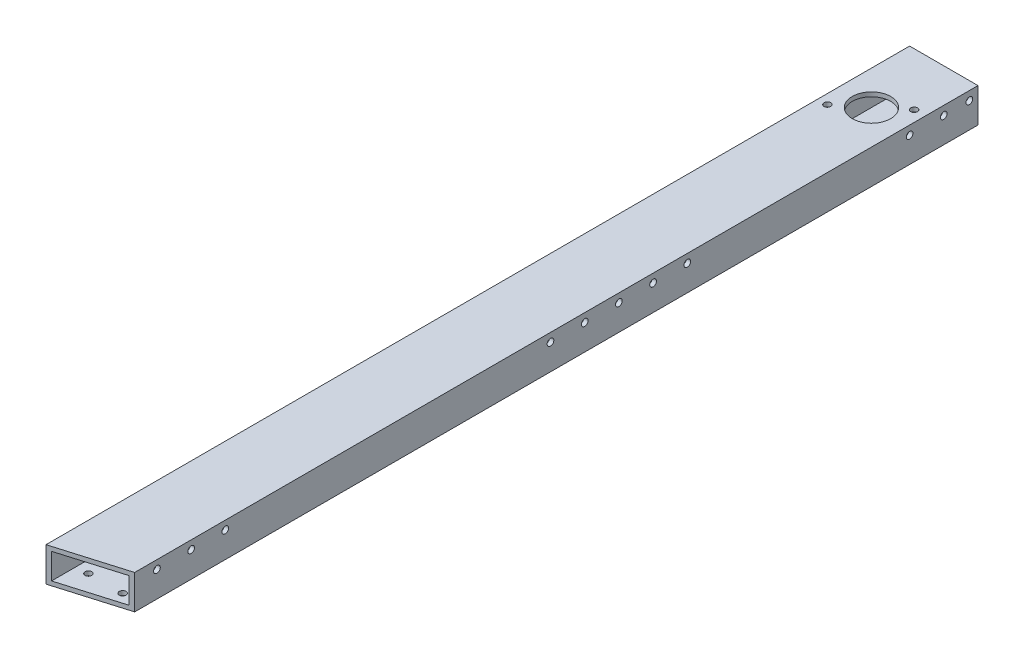
SolidWorks part; units mm, degrees
ref_plane "Front Plane" through (0, 0, 0) normal (0, 0, 1) x (1, 0, 0)
ref_plane "Top Plane" through (0, 0, 0) normal (0, 1, 0) x (1, 0, 0)
ref_plane "Right Plane" through (0, 0, 0) normal (1, 0, 0) x (0, 0, -1)
sketch "Sketch1" plane through (0, 0, 0) normal (0, 0, 1) x (1, 0, 0)
  line L0 (-22.225, 9.525) -> (22.225, 9.525)
  line L2 (-25.4, 12.7) -> (25.4, 12.7)
  line L3 (-25.4, 12.7) -> (-25.4, -12.7)
  line L4 (-25.4, -12.7) -> (25.4, -12.7)
  line L5 (25.4, 12.7) -> (25.4, -12.7)
  line L10 (22.225, 9.525) -> (22.225, -9.525)
  line L11 (-22.225, -9.525) -> (22.225, -9.525)
  line L12 (-22.225, 9.525) -> (-22.225, -9.525)
  point P12 (0, 12.7)
  point P14 (25.4, 0)
  dimension "Wall Thickness" = 3.175
  dimension "Outside Width" = 50.8
  dimension "Outside Height" = 25.4
  dimension "Inside Height" = 19.05
  dimension "Inside Width" = 44.45
sketch "Sketch2" plane through (0, 0, 0) normal (1, 0, 0) x (0, 0, -1)
  line L0 (320.675, 0) -> (-320.675, 0)
  point P4 (0, 0)
  point P7 (-320.675, 0)
  point P10 (320.675, 0)
  dimension "Length" = 641.35
sketch "Sketch3" plane through (0, 0, 0) normal (0, 0, 1) x (1, 0, 0)
  line L21 (25.4, 12.7) -> (-25.4, 12.7)
  line L22 (25.4, -12.7) -> (25.4, 12.7)
  line L23 (-25.4, -12.7) -> (25.4, -12.7)
  line L24 (-25.4, 12.7) -> (-25.4, -12.7)
  line L25 (25.4, 12.7) -> (-25.4, 12.7)
  line L26 (25.4, -12.7) -> (25.4, 12.7)
  line L27 (-25.4, -12.7) -> (25.4, -12.7)
  line L28 (-25.4, 12.7) -> (-25.4, -12.7)
  line L29 (22.225, 9.525) -> (-22.225, 9.525)
  line L30 (22.225, -9.525) -> (22.225, 9.525)
  line L31 (-22.225, -9.525) -> (22.225, -9.525)
  line L32 (-22.225, 9.525) -> (-22.225, -9.525)
  line L33 (22.225, 9.525) -> (-22.225, 9.525)
  line L34 (22.225, -9.525) -> (22.225, 9.525)
  line L35 (-22.225, -9.525) -> (22.225, -9.525)
  line L36 (-22.225, 9.525) -> (-22.225, -9.525)
  dimension "D1" = 0
  dimension "D2" = 0
extrude "Boss-Extrude1" add sketch "Sketch3" along normal up to vertex (320.675 mm away) and the other way up to vertex (320.675 mm away) up to point (0, 0, 320.675) other way up to point (0, 0, -320.675)
sketch "Drawing Reference" plane through (0, 0, 0) normal (1, 0, 0) x (0, 0, -1)
  line L0 (-320.675, 0) -> (320.675, 0) construction
  line L1 (0, -12.7) -> (0, 12.7) construction
  line L2 (-320.675, -12.7) -> (320.675, -12.7) construction
  line L5 (-320.675, 12.7) -> (320.675, 12.7) construction
  point P7 (-284.099, 0)
  point P8 (284.099, 0)
  dimension "D1" = 36.576
sketch "Sketch4" plane through (0, 12.7, 0) normal (0, 1, 0) x (1, 0, 0)
  line L0 (-25.4, -320.675) -> (25.4, -305.6274)
  line L1 (25.4, -320.675) -> (25.4, 320.675) construction
  line L2 (25.4, -320.675) -> (-25.4, -320.675)
  dimension "D1" = 16.5
extrude "Cut-Extrude1" cut sketch "Sketch4" against normal through all and the other way through all flip side to cut
sketch "Sketch8" plane through (0, 12.7, 0) normal (0, 1, 0) x (1, 0, 0)
  line L0 (0, 320.675) -> (0, 266.954) construction
  line L1 (25.4, 320.675) -> (-25.4, 320.675) construction
  circle A0 centre (0, 266.954) radius 14.2875
  dimension "D1" = 53.721
extrude "Cut-Extrude2" cut sketch "Sketch8" against normal through all
sketch "Sketch9" plane through (0, -12.7, 0) normal (0, -1, 0) x (1, 0, 0)
  line L0 (-12.7762, 284.753) -> (-12.7762, 301.263) construction
  line L1 (-12.7762, 301.263) -> (12.6238, 301.263) construction
  line L2 (12.6238, 301.263) -> (12.6238, 284.753) construction
  line L3 (12.6238, 284.753) -> (-12.7762, 284.753) construction
hole_wizard "#10 Clearance Hole1" positions "Sketch10" profile "Sketch11" hole size "#10" standard "ANSI Inch"
sketch "Sketch10" plane through (0, -12.7, 0) normal (0, -1, 0) x (-1, 0, 0)
  point P0 (-12.1168, -284.753)
  point P3 (13.2832, -284.753)
  point P6 (13.2832, -301.263)
  point P9 (-12.1168, -301.263)
sketch "Sketch11" plane through (12.1168, -12.7, 284.753) normal (1, 0, 0) x (0, 0, -1)
  line L0 (0, 0) -> (0, 6.5757)
  line L1 (0, 6.5757) -> (2.4892, 5.08)
  line L2 (2.4892, 5.08) -> (2.4892, 0)
  line L5 (2.4892, 0) -> (0, 0)
  line L10 (0, 6.5757) -> (-2.4892, 5.08) construction
  line L11 (0, -6.35) -> (0, 107.95) construction
  dimension "Hole Dia." = 4.9784
  dimension "Hole Depth" = 5.08
  dimension "Drill Angle" = 118
sketch "Sketch12" plane through (24.893, 0, 0) normal (1, 0, 0) x (0, 0, -1)
  line L0 (320.675, 533.4) -> (-305.6274, 533.4) construction
  line L1 (320.675, 520.7) -> (320.675, 546.1) construction
  line L2 (-305.6274, 546.1) -> (-305.6274, 520.7) construction
hole_wizard "#10 Clearance Hole2" positions "Sketch13" profile "Sketch14" hole size "#10" standard "ANSI Inch"
sketch "Sketch13" plane through (25.4, 0, 0) normal (1, 0, 0) x (0, 0, -1)
  point P0 (314.2868, 6.1483)
  point P3 (295.2368, 6.1483)
  point P6 (269.875, 6.1483)
sketch "Sketch14" plane through (25.4, 6.1483, -314.2868) normal (0, 1, 0) x (0, 0, -1)
  line L0 (0, 0) -> (0, 4.7977)
  line L1 (0, 4.7977) -> (2.4892, 3.302)
  line L2 (2.4892, 3.302) -> (2.4892, 0)
  line L5 (2.4892, 0) -> (0, 0)
  line L10 (0, 4.7977) -> (-2.4892, 3.302) construction
  line L11 (0, -6.35) -> (0, 107.95) construction
  dimension "Hole Dia." = 4.9784
  dimension "Hole Depth" = 3.302
  dimension "Drill Angle" = 118
hole_wizard "#10 Clearance Hole3" positions "Sketch15" profile "Sketch16" hole size "#10" standard "ANSI Inch" end condition through all
sketch "Sketch15" plane through (25.4, 0, 0) normal (1, 0, 0) x (0, 0, -1)
  point P0 (104.775, 6.35)
  point P3 (79.375, 6.35)
  point P6 (53.975, 6.35)
  point P9 (28.575, 6.35)
  point P12 (3.175, 6.35)
  point P24 (-289.0885, 6.3882)
  point P27 (-263.6885, 6.3882)
  point P30 (-238.3267, 6.3882)
sketch "Sketch16" plane through (25.4, 6.35, -104.775) normal (0, 1, 0) x (0, 0, -1)
  line L0 (0, 0) -> (0, 50.8)
  line L1 (0, 50.8) -> (2.4892, 50.8)
  line L2 (2.4892, 50.8) -> (2.4892, 0)
  line L5 (2.4892, 0) -> (0, 0)
  line L11 (0, -6.35) -> (0, 107.95) construction
  dimension "Thru Hole Dia." = 4.9784
  dimension "Thru Hole Depth" = 50.8
sketch "Sketch18" plane through (0, 12.7, 0) normal (0, 1, 0) x (1, 0, 0)
  line L0 (17.279, 281.371) -> (-18.293, 252.537) construction
hole_wizard "#10 Clearance Hole4" positions "Sketch19" profile "Sketch20" hole size "#10" standard "ANSI Inch" end condition through all
sketch "Sketch19" plane through (0, 12.7, 0) normal (0, 1, 0) x (1, 0, 0)
  point P0 (-18.293, 252.537)
  point P3 (17.279, 281.371)
sketch "Sketch20" plane through (-18.293, 12.7, -252.537) normal (1, 0, 0) x (0, 0, 1)
  line L0 (0, 0) -> (0, 25.4)
  line L1 (0, 25.4) -> (5.2197, 25.4)
  line L2 (2.4892, 22.2589) -> (2.4892, 0)
  line L5 (2.4892, 0) -> (0, 0)
  line L7 (5.2197, 25.4) -> (2.4892, 22.2589)
  line L8 (-5.2197, 25.4) -> (-2.4892, 22.2589) construction
  line L11 (0, -6.35) -> (0, 107.95) construction
  dimension "Thru Hole Dia." = 4.9784
  dimension "Thru Hole Depth" = 25.4
  dimension "Far C'Sink Dia." = 10.4394
  dimension "Far C'Sink Angle" = 82
equation "\"D1@Drawing Reference\"=\"Outside Width@Sketch1\" * 0.72"
